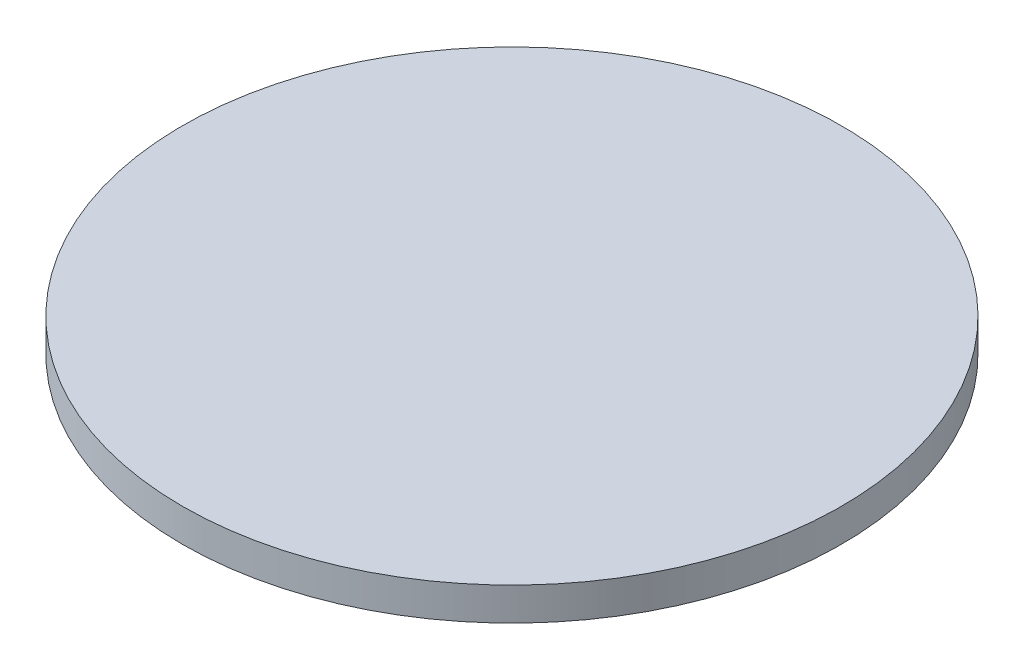
SolidWorks part; units mm, degrees
ref_plane "Front Plane" through (0, 0, 0) normal (0, 0, 1) x (1, 0, 0)
ref_plane "Top Plane" through (0, 0, 0) normal (0, 1, 0) x (1, 0, 0)
ref_plane "Right Plane" through (0, 0, 0) normal (1, 0, 0) x (0, 0, -1)
sketch "Sketch2" plane through (0, 0, 0) normal (0, 1, 0) x (1, 0, 0)
  circle A0 centre (0, 0) radius 35
  dimension "D1" = 70
extrude "Boss-Extrude1" add sketch "Sketch2" along normal blind 3.5
ref_plane "Plane1" through (-4, 0, 0) normal (1, 0, 0) x (0, 0, -1)
sketch "Sketch33" plane through (0, 0, 0) normal (0, -1, 0) x (1, 0, 0)
  circle A0 centre (0, 0) radius 30
  dimension "D1" = 60
extrude "Boss-Extrude3" add sketch "Sketch33" along normal blind 2.2
ref_plane "Plane2" through (0, -4.2, 0) normal (0, -1, 0) x (-1, 0, 0)
sketch "Sketch35" plane through (64.9204, -4.2, -6.6124) normal (0, 1, 0) x (1, 0, 0)
  line L0 (-64.9204, 23.3876) -> (-64.9204, -51.1324) construction
  line L1 (-64.9204, -6.5857) -> (-104.2271, -6.5857) construction
  line L3 (-62.0204, -8.2857) -> (-67.8204, -8.2857)
  line L4 (-62.0204, -8.2857) -> (-62.0204, -4.8857)
  line L5 (-62.0204, -4.8857) -> (-67.8204, -4.8857)
  line L6 (-67.8204, -8.2857) -> (-67.8204, -4.8857)
  circle A0 centre (-64.9204, -6.6124) radius 30 construction
  circle A1 centre (-64.9204, -6.6124) radius 30 construction
  dimension "D1" = 3.4
  dimension "D2" = 5.8
  dimension "D3" = 1.7
  dimension "D4" = 2.9
extrude "Boss-Extrude4" add sketch "Sketch35" against normal blind 6
shell "Shell2" thickness 1 removed face at (0, -10.2, -0.0268) outward yes
sketch "Sketch39" plane through (0, -2.2, 0) normal (0, -1, 0) x (-1, 0, 0)
  circle A0 centre (0, 0) radius 4.25
  circle A1 centre (0, 0) radius 5.5
extrude "Boss-Extrude5" add sketch "Sketch39" along normal blind 9
sketch "Sketch41" plane through (0, -10.2, 0) normal (0, -1, 0) x (-1, 0, 0)
  line L0 (0, 1.7268) -> (0, -7.344) construction
  line L1 (-2.9, 1.7268) -> (2.9, 1.7268) construction
  circle A0 centre (0, 0) radius 3.7
  circle A1 centre (0, 0) radius 4.5
extrude "Boss-Extrude6" add sketch "Sketch41" along normal blind 4
